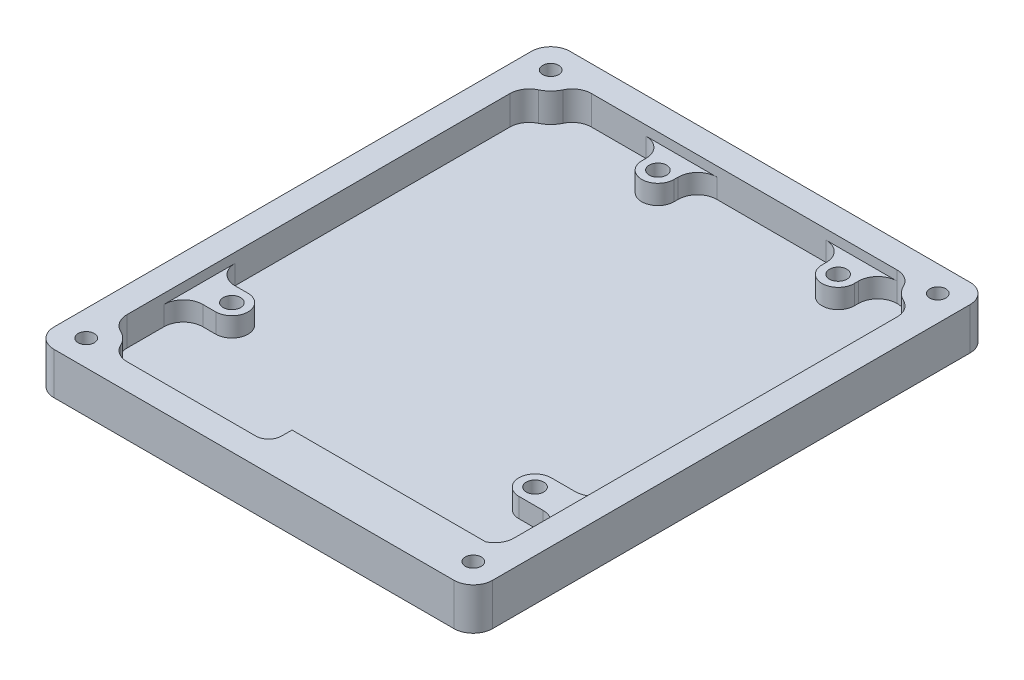
SolidWorks part; units mm, degrees
ref_plane "Front" through (0, 0, 0) normal (0, 0, 1) x (1, 0, 0)
ref_plane "Top" through (0, 0, 0) normal (0, 1, 0) x (1, 0, 0)
ref_plane "Right" through (0, 0, 0) normal (1, 0, 0) x (0, 0, -1)
sketch "스케치1" plane through (0, 0, 0) normal (0, 1, 0) x (1, 0, 0)
  line L0 (25.8154, -33.6766) -> (-27.5246, -33.6766) construction
  line L1 (25.8154, -33.6766) -> (25.8154, 32.3634) construction
  line L2 (20.7354, 34.9034) -> (-12.0306, 34.9034) construction
  line L3 (-27.5246, -33.6766) -> (-27.5246, 32.3634) construction
  line L4 (-27.5246, 32.3634) -> (-14.5706, 32.3634) construction
  line L5 (-14.5706, 32.3634) -> (-12.0306, 34.9034) construction
  line L6 (20.7354, 34.9034) -> (23.2754, 32.3634) construction
  line L7 (23.2754, 32.3634) -> (25.8154, 32.3634) construction
  line L8 (-30, 36) -> (30, -36) construction
  line L9 (-26, 36) -> (26, 36)
  line L10 (-30, 32) -> (-30, -32)
  line L11 (-26, -36) -> (26, -36)
  line L12 (30, 32) -> (30, -32)
  line L13 (-30, 0) -> (30, 0) construction
  line L14 (-34, 37) -> (-34, -37)
  line L15 (-31, -40) -> (31, -40)
  line L16 (34, 37) -> (34, -37)
  line L17 (-31, 40) -> (31, 40)
  line L18 (-34, -40) -> (34, -40) construction
  line L19 (-30, 36) -> (30, 36) construction
  line L20 (-30, 36) -> (-30, -36) construction
  line L21 (30, 36) -> (30, -36) construction
  line L22 (-30, -36) -> (30, -36) construction
  line L23 (-34, 40) -> (-34, -40) construction
  line L24 (-34, 40) -> (34, 40) construction
  line L25 (34, 40) -> (34, -40) construction
  circle A0 centre (18.1954, 32.3634) radius 1.5875 construction
  circle A1 centre (-9.7446, 32.3634) radius 1.5875 construction
  circle A2 centre (23.2754, -19.7066) radius 1.5875 construction
  circle A3 centre (-24.9846, -18.4366) radius 1.5875 construction
  arc A4 (26, 36) -> (30, 32) centre (30, 36) ccw
  arc A5 (-30, 32) -> (-26, 36) centre (-30, 36) ccw
  arc A6 (-26, -36) -> (-30, -32) centre (-30, -36) ccw
  arc A7 (30, -32) -> (26, -36) centre (30, -36) ccw
  arc A8 (-31, -40) -> (-34, -37) centre (-31, -37) cw
  arc A9 (-34, 37) -> (-31, 40) centre (-31, 37) cw
  arc A10 (31, 40) -> (34, 37) centre (31, 37) cw
  arc A11 (34, -37) -> (31, -40) centre (31, -37) cw
  dimension "D6" = 3.175
  dimension "D14" = 3
  dimension "D1" = 53.34
  dimension "D2" = 2.54
  dimension "D3" = 45
  dimension "D4" = 40.386
  dimension "D5" = 45
  dimension "D7" = 35.56
  dimension "D8" = 7.62
  dimension "D9" = 2.54
  dimension "D10" = 50.8
  dimension "D11" = 72
  dimension "D12" = 60
  dimension "D13" = 4
extrude "보스-돌출1" add sketch "스케치1" along normal blind 7.5
sketch "스케치3" plane through (0, 0, 0) normal (0, -1, 0) x (1, 0, 0)
  line L4 (-34, 37) -> (-34, -37)
  line L5 (-31, -40) -> (31, -40)
  line L6 (34, -37) -> (34, 37)
  line L7 (31, 40) -> (-31, 40)
  line L8 (-34, 37) -> (-34, -37)
  line L9 (-31, -40) -> (31, -40)
  line L10 (34, -37) -> (34, 37)
  line L11 (31, 40) -> (-31, 40)
  arc A4 (-31, 40) -> (-34, 37) centre (-31, 37) ccw
  arc A5 (-34, -37) -> (-31, -40) centre (-31, -37) ccw
  arc A6 (31, -40) -> (34, -37) centre (31, -37) ccw
  arc A7 (34, 37) -> (31, 40) centre (31, 37) ccw
  arc A8 (-31, 40) -> (-34, 37) centre (-31, 37) ccw
  arc A9 (-34, -37) -> (-31, -40) centre (-31, -37) ccw
  arc A10 (31, -40) -> (34, -37) centre (31, -37) ccw
  arc A11 (34, 37) -> (31, 40) centre (31, 37) ccw
  dimension "D1" = 0
extrude "보스-돌출2" add sketch "스케치3" against normal blind 3
sketch "스케치4" plane through (0, 3, 0) normal (0, 1, 0) x (1, 0, 0)
  line L1 (23.2754, -17.2066) -> (31.2754, -17.2066)
  line L3 (23.2754, -22.2066) -> (31.2754, -22.2066)
  line L4 (31.2754, -17.2066) -> (31.2754, -22.2066)
  line L5 (-24.9846, -20.9366) -> (-30.9846, -20.9366)
  line L7 (-24.9846, -15.9366) -> (-30.9846, -15.9366)
  line L8 (-30.9846, -20.9366) -> (-30.9846, -15.9366)
  line L10 (15.6954, 32.3634) -> (15.6954, 38.3634)
  line L11 (15.6954, 38.3634) -> (20.6954, 38.3634)
  line L12 (20.6954, 32.3634) -> (20.6954, 38.3634)
  line L13 (-12.2446, 38.3634) -> (-7.2446, 38.3634)
  line L14 (-12.2446, 38.3634) -> (-12.2446, 32.3634)
  line L16 (-7.2446, 38.3634) -> (-7.2446, 32.3634)
  arc A0 (15.6954, 32.3634) -> (20.6954, 32.3634) centre (18.1954, 32.3634) ccw
  arc A1 (-12.2446, 32.3634) -> (-7.2446, 32.3634) centre (-9.7446, 32.3634) ccw
  arc A2 (23.2754, -17.2066) -> (23.2754, -22.2066) centre (23.2754, -19.7066) ccw
  arc A3 (-24.9846, -20.9366) -> (-24.9846, -15.9366) centre (-24.9846, -18.4366) ccw
  dimension "D1" = 5
  dimension "D3" = 6
  dimension "D4" = 8
  dimension "D5" = 6
extrude "보스-돌출3" add sketch "스케치4" along normal blind 3
fillet "필렛3" radius 3 16 edges at (30, 4.5, 17.2066) (30, 4.5, 22.2066) (-30, 4.5, 15.9366) (-30, 4.5, 20.9366) (-7.2446, 4.5, -36) (-12.2446, 4.5, -36) (20.6954, 4.5, -36) (15.6954, 4.5, -36) (26, 5.25, 36) (30, 5.25, 32) (30, 5.25, -32) (26, 5.25, -36) (-26, 5.25, 36) (-30, 5.25, 32) (-26, 5.25, -36) (-30, 5.25, -32)
sketch "스케치5" plane through (0, 7.5, 0) normal (0, 1, 0) x (1, 0, 0)
  line L1 (28.2857, -32.386) -> (-1.7143, -32.386)
  line L2 (28.2857, -32.386) -> (28.2857, -36.886)
  line L3 (28.2857, -36.886) -> (-1.7143, -36.886)
  line L4 (-1.7143, -32.386) -> (-1.7143, -36.886)
  dimension "D1" = 4.5
  dimension "D2" = 30
extrude "보스-돌출4" add sketch "스케치5" against normal up to next
sketch "스케치8" plane through (0, 7.5, 0) normal (0, 1, 0) x (1, 0, 0)
  line L0 (-34, 0) -> (34, 0) construction
  line L1 (-34, 37) -> (-34, -37) construction
  line L2 (34, -37) -> (34, 37) construction
  line L3 (0, 40) -> (0, -40) construction
  line L4 (31, 40) -> (-31, 40) construction
  line L5 (-31, -40) -> (31, -40) construction
  circle A1 centre (30, -36) radius 1.25
  circle A2 centre (-30, -36) radius 1.25
  circle A8 centre (-30, 36) radius 1.25
  arc A9 (-28.2857, 32.386) -> (-26.386, 34.2857) centre (-30, 36) ccw construction
  circle A10 centre (30, 36) radius 1.25
  dimension "D1" = 2.5
extrude "컷-돌출2" cut sketch "스케치8" against normal blind 5
sketch "스케치6" plane through (0, 7.5, 0) normal (0, 1, 0) x (1, 0, 0)
  line L4 (-31, -40) -> (31, -40)
  line L5 (34, -37) -> (34, 37)
  line L6 (31, 40) -> (-31, 40)
  line L7 (-34, 37) -> (-34, -37)
  line L8 (-31, -40) -> (31, -40)
  line L9 (34, -37) -> (34, 37)
  line L10 (31, 40) -> (-31, 40)
  line L11 (-34, 37) -> (-34, -37)
  arc A4 (-34, -37) -> (-31, -40) centre (-31, -37) ccw
  arc A5 (31, -40) -> (34, -37) centre (31, -37) ccw
  arc A6 (34, 37) -> (31, 40) centre (31, 37) ccw
  arc A7 (-31, 40) -> (-34, 37) centre (-31, 37) ccw
  arc A8 (-34, -37) -> (-31, -40) centre (-31, -37) ccw
  arc A9 (31, -40) -> (34, -37) centre (31, -37) ccw
  arc A10 (34, 37) -> (31, 40) centre (31, 37) ccw
  arc A11 (-31, 40) -> (-34, 37) centre (-31, 37) ccw
  dimension "D1" = 0
sketch "스케치7" plane through (0, 3, 0) normal (0, 1, 0) x (1, 0, 0)
  line L17 (-23.6754, -36) -> (-1.7143, -36)
  line L18 (-1.7143, -36) -> (-1.7143, -32.386)
  line L19 (-1.7143, -32.386) -> (28.2857, -32.386)
  line L20 (30, -29.6754) -> (30, -25.2066)
  line L21 (27, -22.2066) -> (23.2754, -22.2066)
  line L22 (23.2754, -17.2066) -> (27, -17.2066)
  line L23 (30, -14.2066) -> (30, 29.6754)
  line L24 (20.6954, 33) -> (20.6954, 32.3634)
  line L25 (15.6954, 32.3634) -> (15.6954, 33)
  line L26 (12.6954, 36) -> (-4.2446, 36)
  line L27 (-7.2446, 33) -> (-7.2446, 32.3634)
  line L28 (-12.2446, 32.3634) -> (-12.2446, 33)
  line L29 (-15.2446, 36) -> (-23.6754, 36)
  line L30 (-30, 29.6754) -> (-30, -12.9366)
  line L31 (-27, -15.9366) -> (-24.9846, -15.9366)
  line L32 (-24.9846, -20.9366) -> (-27, -20.9366)
  line L33 (-30, -23.9366) -> (-30, -29.6754)
  line L34 (-23.6754, -36) -> (-1.7143, -36)
  line L35 (-1.7143, -36) -> (-1.7143, -32.386)
  line L36 (-1.7143, -32.386) -> (28.2857, -32.386)
  line L37 (30, -29.6754) -> (30, -25.2066)
  line L38 (27, -22.2066) -> (23.2754, -22.2066)
  line L39 (23.2754, -17.2066) -> (27, -17.2066)
  line L40 (30, -14.2066) -> (30, 29.6754)
  line L41 (20.6954, 33) -> (20.6954, 32.3634)
  line L42 (15.6954, 32.3634) -> (15.6954, 33)
  line L43 (12.6954, 36) -> (-4.2446, 36)
  line L44 (-7.2446, 33) -> (-7.2446, 32.3634)
  line L45 (-12.2446, 32.3634) -> (-12.2446, 33)
  line L46 (-15.2446, 36) -> (-23.6754, 36)
  line L47 (-30, 29.6754) -> (-30, -12.9366)
  line L48 (-27, -15.9366) -> (-24.9846, -15.9366)
  line L49 (-24.9846, -20.9366) -> (-27, -20.9366)
  line L50 (-30, -23.9366) -> (-30, -29.6754)
  arc A22 (28.2857, -32.386) -> (30, -29.6754) centre (27, -29.6754) ccw
  arc A23 (30, -25.2066) -> (27, -22.2066) centre (27, -25.2066) ccw
  arc A24 (23.2754, -17.2066) -> (23.2754, -22.2066) centre (23.2754, -19.7066) ccw
  arc A25 (27, -17.2066) -> (30, -14.2066) centre (27, -14.2066) ccw
  arc A26 (30, 29.6754) -> (28.2857, 32.386) centre (27, 29.6754) ccw
  arc A27 (26.386, 34.2857) -> (28.2857, 32.386) centre (30, 36) ccw
  arc A28 (26.386, 34.2857) -> (23.6854, 36) centre (23.6754, 33) ccw
  arc A29 (23.6854, 36) -> (20.6954, 33) centre (23.6954, 33) ccw
  arc A30 (15.6954, 32.3634) -> (20.6954, 32.3634) centre (18.1954, 32.3634) ccw
  arc A31 (15.6954, 33) -> (12.6954, 36) centre (12.6954, 33) ccw
  arc A32 (-4.2446, 36) -> (-7.2446, 33) centre (-4.2446, 33) ccw
  arc A33 (-12.2446, 32.3634) -> (-7.2446, 32.3634) centre (-9.7446, 32.3634) ccw
  arc A34 (-12.2446, 33) -> (-15.2446, 36) centre (-15.2446, 33) ccw
  arc A35 (-23.6754, 36) -> (-26.386, 34.2857) centre (-23.6754, 33) ccw
  arc A36 (-28.2857, 32.386) -> (-26.386, 34.2857) centre (-30, 36) ccw
  arc A37 (-28.2857, 32.386) -> (-30, 29.6754) centre (-27, 29.6754) ccw
  arc A38 (-30, -12.9366) -> (-27, -15.9366) centre (-27, -12.9366) ccw
  arc A39 (-24.9846, -20.9366) -> (-24.9846, -15.9366) centre (-24.9846, -18.4366) ccw
  arc A40 (-27, -20.9366) -> (-30, -23.9366) centre (-27, -23.9366) ccw
  arc A41 (-30, -29.6754) -> (-28.2857, -32.386) centre (-27, -29.6754) ccw
  arc A42 (-26.386, -34.2857) -> (-28.2857, -32.386) centre (-30, -36) ccw
  arc A43 (-26.386, -34.2857) -> (-23.6754, -36) centre (-23.6754, -33) ccw
  arc A44 (28.2857, -32.386) -> (30, -29.6754) centre (27, -29.6754) ccw
  arc A45 (30, -25.2066) -> (27, -22.2066) centre (27, -25.2066) ccw
  arc A46 (23.2754, -17.2066) -> (23.2754, -22.2066) centre (23.2754, -19.7066) ccw
  arc A47 (27, -17.2066) -> (30, -14.2066) centre (27, -14.2066) ccw
  arc A48 (30, 29.6754) -> (28.2857, 32.386) centre (27, 29.6754) ccw
  arc A49 (26.386, 34.2857) -> (28.2857, 32.386) centre (30, 36) ccw
  arc A50 (26.386, 34.2857) -> (23.6854, 36) centre (23.6754, 33) ccw
  arc A51 (23.6854, 36) -> (20.6954, 33) centre (23.6954, 33) ccw
  arc A52 (15.6954, 32.3634) -> (20.6954, 32.3634) centre (18.1954, 32.3634) ccw
  arc A53 (15.6954, 33) -> (12.6954, 36) centre (12.6954, 33) ccw
  arc A54 (-4.2446, 36) -> (-7.2446, 33) centre (-4.2446, 33) ccw
  arc A55 (-12.2446, 32.3634) -> (-7.2446, 32.3634) centre (-9.7446, 32.3634) ccw
  arc A56 (-12.2446, 33) -> (-15.2446, 36) centre (-15.2446, 33) ccw
  arc A57 (-23.6754, 36) -> (-26.386, 34.2857) centre (-23.6754, 33) ccw
  arc A58 (-28.2857, 32.386) -> (-26.386, 34.2857) centre (-30, 36) ccw
  arc A59 (-28.2857, 32.386) -> (-30, 29.6754) centre (-27, 29.6754) ccw
  arc A60 (-30, -12.9366) -> (-27, -15.9366) centre (-27, -12.9366) ccw
  arc A61 (-24.9846, -20.9366) -> (-24.9846, -15.9366) centre (-24.9846, -18.4366) ccw
  arc A62 (-27, -20.9366) -> (-30, -23.9366) centre (-27, -23.9366) ccw
  arc A63 (-30, -29.6754) -> (-28.2857, -32.386) centre (-27, -29.6754) ccw
  arc A64 (-26.386, -34.2857) -> (-28.2857, -32.386) centre (-30, -36) ccw
  arc A65 (-26.386, -34.2857) -> (-23.6754, -36) centre (-23.6754, -33) ccw
  dimension "D1" = 0
sketch "스케치9" plane through (0, 7.5, 0) normal (0, 1, 0) x (1, 0, 0)
  line L4 (-31, -40) -> (31, -40)
  line L5 (34, -37) -> (34, 37)
  line L6 (31, 40) -> (-31, 40)
  line L7 (-34, 37) -> (-34, -37)
  line L8 (-31, -40) -> (31, -40)
  line L9 (34, -37) -> (34, 37)
  line L10 (31, 40) -> (-31, 40)
  line L11 (-34, 37) -> (-34, -37)
  arc A4 (-34, -37) -> (-31, -40) centre (-31, -37) ccw
  arc A5 (31, -40) -> (34, -37) centre (31, -37) ccw
  arc A6 (34, 37) -> (31, 40) centre (31, 37) ccw
  arc A7 (-31, 40) -> (-34, 37) centre (-31, 37) ccw
  arc A8 (-34, -37) -> (-31, -40) centre (-31, -37) ccw
  arc A9 (31, -40) -> (34, -37) centre (31, -37) ccw
  arc A10 (34, 37) -> (31, 40) centre (31, 37) ccw
  arc A11 (-31, 40) -> (-34, 37) centre (-31, 37) ccw
  dimension "D1" = 0
sketch "스케치10" plane through (0, 7.5, 0) normal (0, 1, 0) x (1, 0, 0)
  line L0 (-12.2446, 33) -> (-12.2446, 32.3634) construction
  line L1 (-7.2446, 32.3634) -> (-7.2446, 33) construction
  line L2 (15.6954, 33) -> (15.6954, 32.3634) construction
  line L3 (20.6954, 32.3634) -> (20.6954, 33) construction
  line L4 (-31, -40) -> (31, -40)
  line L5 (34, -37) -> (34, 37)
  line L6 (31, 40) -> (-31, 40)
  line L7 (-34, 37) -> (-34, -37)
  line L8 (-31, -40) -> (31, -40)
  line L9 (34, -37) -> (34, 37)
  line L10 (31, 40) -> (-31, 40)
  line L11 (-34, 37) -> (-34, -37)
  line L12 (27, -17.2066) -> (23.2754, -17.2066) construction
  line L13 (23.2754, -22.2066) -> (27, -22.2066) construction
  line L14 (-1.7143, -32.386) -> (28.2857, -32.386)
  line L15 (-1.7143, -36) -> (-1.7143, -32.386)
  line L16 (-23.6754, -36) -> (-1.7143, -36)
  line L17 (-30, 29.6754) -> (-30, -29.6754)
  line L18 (23.6754, 36) -> (-23.6754, 36)
  line L19 (30, -29.6754) -> (30, 29.6754)
  line L20 (-1.7143, -32.386) -> (28.2857, -32.386)
  line L21 (-1.7143, -36) -> (-1.7143, -32.386)
  line L22 (-23.6754, -36) -> (-1.7143, -36)
  line L23 (-30, 29.6754) -> (-30, -12.9366)
  line L24 (12.6954, 36) -> (-4.2446, 36)
  line L25 (30, -29.6754) -> (30, -25.2066)
  line L26 (-24.9846, -15.9366) -> (-27, -15.9366) construction
  line L27 (-27, -20.9366) -> (-24.9846, -20.9366) construction
  line L28 (-12.2446, 33) -> (-12.2446, 32.3634)
  line L29 (-7.2446, 32.3634) -> (-7.2446, 33)
  line L30 (15.6954, 33) -> (15.6954, 32.3634)
  line L31 (20.6954, 32.3634) -> (20.6954, 33)
  line L32 (27, -17.2066) -> (23.2754, -17.2066)
  line L33 (23.2754, -22.2066) -> (27, -22.2066)
  line L34 (-24.9846, -15.9366) -> (-27, -15.9366)
  line L35 (-27, -20.9366) -> (-24.9846, -20.9366)
  line L36 (-15.2446, 36) -> (-23.6754, 36)
  line L37 (-30, -23.9366) -> (-30, -29.6754)
  line L38 (30, -14.2066) -> (30, 29.6754)
  arc A0 (-12.2446, 33) -> (-15.2446, 36) centre (-15.2446, 33) ccw construction
  arc A1 (-12.2446, 32.3634) -> (-7.2446, 32.3634) centre (-9.7446, 32.3634) ccw construction
  arc A2 (-4.2446, 36) -> (-7.2446, 33) centre (-4.2446, 33) ccw construction
  arc A3 (15.6954, 33) -> (12.6954, 36) centre (12.6954, 33) ccw construction
  arc A4 (-34, -37) -> (-31, -40) centre (-31, -37) ccw
  arc A5 (31, -40) -> (34, -37) centre (31, -37) ccw
  arc A6 (34, 37) -> (31, 40) centre (31, 37) ccw
  arc A7 (-31, 40) -> (-34, 37) centre (-31, 37) ccw
  arc A8 (-34, -37) -> (-31, -40) centre (-31, -37) ccw
  arc A9 (31, -40) -> (34, -37) centre (31, -37) ccw
  arc A10 (34, 37) -> (31, 40) centre (31, 37) ccw
  arc A11 (-31, 40) -> (-34, 37) centre (-31, 37) ccw
  arc A12 (15.6954, 32.3634) -> (20.6954, 32.3634) centre (18.1954, 32.3634) ccw construction
  arc A13 (23.6854, 36) -> (20.6954, 33) centre (23.6954, 33) ccw construction
  arc A14 (27, -17.2066) -> (30, -14.2066) centre (27, -14.2066) ccw construction
  arc A15 (23.2754, -17.2066) -> (23.2754, -22.2066) centre (23.2754, -19.7066) ccw construction
  arc A16 (30, -25.2066) -> (27, -22.2066) centre (27, -25.2066) ccw construction
  arc A17 (-30, -12.9366) -> (-27, -15.9366) centre (-27, -12.9366) ccw construction
  arc A18 (28.2857, -32.386) -> (30, -29.6754) centre (27, -29.6754) ccw
  arc A19 (-26.386, -34.2857) -> (-23.6754, -36) centre (-23.6754, -33) ccw
  arc A20 (-26.386, -34.2857) -> (-28.2857, -32.386) centre (-30, -36) ccw
  arc A21 (-30, -29.6754) -> (-28.2857, -32.386) centre (-27, -29.6754) ccw
  arc A22 (-28.2857, 32.386) -> (-30, 29.6754) centre (-27, 29.6754) ccw
  arc A23 (-28.2857, 32.386) -> (-26.386, 34.2857) centre (-30, 36) ccw
  arc A24 (-23.6754, 36) -> (-26.386, 34.2857) centre (-23.6754, 33) ccw
  arc A25 (26.386, 34.2857) -> (23.6754, 36) centre (23.6754, 33) ccw
  arc A26 (26.386, 34.2857) -> (28.2857, 32.386) centre (30, 36) ccw
  arc A27 (30, 29.6754) -> (28.2857, 32.386) centre (27, 29.6754) ccw
  arc A28 (28.2857, -32.386) -> (30, -29.6754) centre (27, -29.6754) ccw
  arc A29 (-26.386, -34.2857) -> (-23.6754, -36) centre (-23.6754, -33) ccw
  arc A30 (-26.386, -34.2857) -> (-28.2857, -32.386) centre (-30, -36) ccw
  arc A31 (-30, -29.6754) -> (-28.2857, -32.386) centre (-27, -29.6754) ccw
  arc A32 (-28.2857, 32.386) -> (-30, 29.6754) centre (-27, 29.6754) ccw
  arc A33 (-28.2857, 32.386) -> (-26.386, 34.2857) centre (-30, 36) ccw
  arc A34 (-23.6754, 36) -> (-26.386, 34.2857) centre (-23.6754, 33) ccw
  arc A35 (26.386, 34.2857) -> (23.6754, 36) centre (23.6754, 33) ccw
  arc A36 (26.386, 34.2857) -> (28.2857, 32.386) centre (30, 36) ccw
  arc A37 (30, 29.6754) -> (28.2857, 32.386) centre (27, 29.6754) ccw
  arc A38 (-27, -20.9366) -> (-30, -23.9366) centre (-27, -23.9366) ccw construction
  arc A39 (-24.9846, -20.9366) -> (-24.9846, -15.9366) centre (-24.9846, -18.4366) ccw construction
  arc A40 (-12.2446, 33) -> (-15.2446, 36) centre (-15.2446, 33) ccw
  arc A41 (-12.2446, 32.3634) -> (-7.2446, 32.3634) centre (-9.7446, 32.3634) ccw
  arc A42 (-4.2446, 36) -> (-7.2446, 33) centre (-4.2446, 33) ccw
  arc A43 (15.6954, 33) -> (12.6954, 36) centre (12.6954, 33) ccw
  arc A44 (15.6954, 32.3634) -> (20.6954, 32.3634) centre (18.1954, 32.3634) ccw
  arc A45 (23.6854, 36) -> (20.6954, 33) centre (23.6954, 33) ccw
  arc A46 (27, -17.2066) -> (30, -14.2066) centre (27, -14.2066) ccw
  arc A47 (23.2754, -17.2066) -> (23.2754, -22.2066) centre (23.2754, -19.7066) ccw
  arc A48 (30, -25.2066) -> (27, -22.2066) centre (27, -25.2066) ccw
  arc A49 (-30, -12.9366) -> (-27, -15.9366) centre (-27, -12.9366) ccw
  arc A50 (-27, -20.9366) -> (-30, -23.9366) centre (-27, -23.9366) ccw
  arc A51 (-24.9846, -20.9366) -> (-24.9846, -15.9366) centre (-24.9846, -18.4366) ccw
  circle A52 centre (-30, -36) radius 1.25 construction
  circle A53 centre (-30, -36) radius 1.25
  circle A54 centre (30, -36) radius 1.25 construction
  circle A55 centre (30, -36) radius 1.25
  circle A56 centre (-30, 36) radius 1.25 construction
  circle A57 centre (-30, 36) radius 1.25
  circle A58 centre (30, 36) radius 1.25 construction
  circle A59 centre (30, 36) radius 1.25
  dimension "D1" = 0
  dimension "D2" = 0
sketch "스케치16" plane through (0, 0, 0) normal (0, -1, 0) x (1, 0, 0)
  line L5 (0, 40) -> (0, -40)
  line L7 (-34, 0) -> (34, 0)
  line L9 (-34, 37) -> (-34, -37)
  line L10 (-31, -40) -> (31, -40)
  line L11 (34, -37) -> (34, 37)
  line L12 (31, 40) -> (-31, 40)
  line L13 (-34, 37) -> (-34, -37)
  line L14 (-31, -40) -> (31, -40)
  line L15 (34, -37) -> (34, 37)
  line L16 (31, 40) -> (-31, 40)
  arc A4 (-31, 40) -> (-34, 37) centre (-31, 37) ccw
  arc A5 (-34, -37) -> (-31, -40) centre (-31, -37) ccw
  arc A6 (31, -40) -> (34, -37) centre (31, -37) ccw
  arc A7 (34, 37) -> (31, 40) centre (31, 37) ccw
  arc A8 (-31, 40) -> (-34, 37) centre (-31, 37) ccw
  arc A9 (-34, -37) -> (-31, -40) centre (-31, -37) ccw
  arc A10 (31, -40) -> (34, -37) centre (31, -37) ccw
  arc A11 (34, 37) -> (31, 40) centre (31, 37) ccw
  dimension "D1" = 0
chamfer "모따기1" distance 3 distance2 1 8 edges at (0, 0, -40) (-33.1213, 0, -39.1213) (33.1213, 0, -39.1213) (-34, 0, 0) (34, 0, 0) (-33.1213, 0, 39.1213) (33.1213, 0, 39.1213) (0, 0, 40) first distance on face at (0, 0, 0)
sketch "스케치19" plane through (0, 0, 0) normal (0, -1, 0) x (1, 0, 0)
  line L1 (-21.6441, 40) -> (-26.6441, 40)
  line L2 (-21.6441, 40) -> (-21.6441, -18)
  line L3 (-21.6441, -40) -> (-26.6441, -40)
  line L4 (-26.6441, 40) -> (-26.6441, -18)
  line L7 (-34, -20) -> (-28.6441, -20)
  line L8 (-34, -20) -> (-34, -25)
  line L9 (-34, -25) -> (-28.6441, -25)
  line L10 (34, -20) -> (34, -25)
  line L12 (-26.6441, -27) -> (-26.6441, -40)
  line L13 (-19.6441, -20) -> (34, -20)
  line L14 (-21.6441, -27) -> (-21.6441, -40)
  line L15 (-19.6441, -25) -> (34, -25)
  line L16 (31, -40) -> (-31, -40) construction
  line L17 (-31, 40) -> (31, 40) construction
  line L18 (-34, -37) -> (-34, 37) construction
  line L19 (34, 37) -> (34, -37) construction
  arc A0 (-21.6441, -27) -> (-19.6441, -25) centre (-19.6441, -27) cw
  arc A1 (-26.6441, -27) -> (-28.6441, -25) centre (-28.6441, -27) ccw
  arc A2 (-28.6441, -20) -> (-26.6441, -18) centre (-28.6441, -18) ccw
  arc A3 (-19.6441, -20) -> (-21.6441, -18) centre (-19.6441, -18) cw
  point P4 (-21.9648, 39.6402)
  point P5 (-22.1596, -37)
  point P6 (0, 0)
  point P7 (0, 0)
  point P12 (0, 0)
  point P13 (0, 0)
  point P14 (0, 0)
  point P15 (-34, -22.5)
  point P20 (-21.2854, 37)
  point P21 (-26.6441, 39.6402)
  point P22 (-21.7347, 37)
  point P23 (0, 0)
  point P24 (0, 0)
  point P25 (-21.8422, -38.8374)
  point P30 (0, 0)
  point P31 (0, 0)
  point P38 (-21.6441, -25)
  dimension "D4" = 2
  dimension "D1" = 5
  dimension "D2" = 5
  dimension "D3" = 60
extrude "컷-돌출4" cut sketch "스케치19" against normal blind 0.1
sketch "스케치17" plane through (0, 0, 0) normal (0, -1, 0) x (1, 0, 0)
  line L0 (-19.6441, -20) -> (31, -20) construction
  line L1 (-7.5115, 34.2362) -> (-7.5115, 5.3188) construction
  line L2 (31, -20) -> (-19.6441, -20) construction
  line L3 (-19.6441, -30) -> (29.4015, -30) construction
  text T0 "NEXONECORE" font "Century Gothic" height 4.5
  dimension "D1" = 10
extrude "컷-돌출3" cut sketch "스케치17" against normal blind 0.2
sketch "스케치20" plane through (0, 6, 0) normal (0, 1, 0) x (1, 0, 0)
  circle A0 centre (23.2754, -19.7066) radius 1.35
  arc A1 (23.2754, -17.2066) -> (23.2754, -22.2066) centre (23.2754, -19.7066) ccw construction
  circle A2 centre (-24.9846, -18.4366) radius 1.35
  arc A3 (-24.9846, -20.9366) -> (-24.9846, -15.9366) centre (-24.9846, -18.4366) ccw construction
  circle A4 centre (18.1954, 32.3634) radius 1.35
  circle A5 centre (-9.7446, 32.3634) radius 1.35
  arc A6 (15.6954, 32.3634) -> (20.6954, 32.3634) centre (18.1954, 32.3634) ccw construction
  arc A7 (-12.2446, 32.3634) -> (-7.2446, 32.3634) centre (-9.7446, 32.3634) ccw construction
extrude "컷-돌출5" cut sketch "스케치20" against normal blind 5
fillet "필렛4" radius 2 1 edges at (-1.7143, 5.25, 36)
